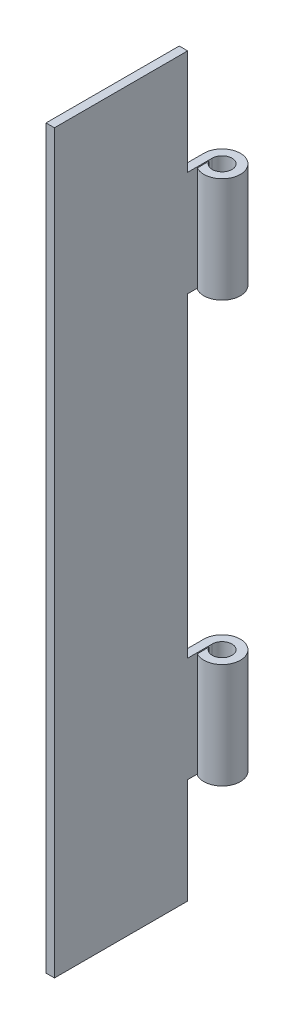
SolidWorks part; units mm, degrees
ref_plane "Front Plane" through (0, 0, 0) normal (0, 0, 1) x (1, 0, 0)
ref_plane "Top Plane" through (0, 0, 0) normal (0, 1, 0) x (1, 0, 0)
ref_plane "Right Plane" through (0, 0, 0) normal (1, 0, 0) x (0, 0, -1)
sketch "Sketch1" plane through (0, 0, 0) normal (1, 0, 0) x (0, 0, -1)
  line L0 (0, 0) -> (0, 88.9) construction
  line L1 (0, 0) -> (19.05, 0) construction
  line L2 (9.144, 12.7) -> (13.1064, 12.7) construction
  line L3 (0, 0) -> (-19.05, 0) construction
  point P3 (11.1252, 12.7)
  point P5 (11.1252, 76.2)
  point P6 (0, 12.7)
  point P9 (-101.6, 88.9)
  point P10 (11.1252, 12.7)
  point P11 (-25.4, 88.9)
  point P12 (-177.8, 88.9)
  point P13 (-11.1252, 76.2)
  point P14 (-11.1252, 12.7)
  dimension "Knuckle Length" = 12.7
  dimension "Length Corner" = 12.7
  dimension "Height Corner" = 7.9248
  dimension "Overall Width" = 38.1
  dimension "Leaf Height" = 88.9
  dimension "MTG Dia" = 3.9624
  dimension "Num Holes" = 101.6
  dimension "Spring Knuckles" = 25.4
  dimension "Num Knuckles" = 177.8
  dimension "D2" = 7.9248
  dimension "Length Corner 2" = 12.7
  dimension "D4" = 12.7
sketch "Sketch2" plane through (0, 0, 0) normal (0, 1, 0) x (1, 0, 0)
  line L0 (1.016, 0) -> (3.3973, 0) construction
  line L1 (0, 19.05) -> (1.016, 19.05) construction
  line L2 (-0.889, 16.1766) -> (0, 16.1766) construction
  line L3 (2.2066, 1.1906) -> (2.2066, 2.2066) construction
  line L5 (2.2066, 2.2066) -> (2.2066, 16.1766) construction
  circle A0 centre (2.2066, 0) radius 1.1906 construction
  point P9 (2.2066, 1.3176)
  point P10 (1.143, 16.1766)
  dimension "Leaf Thickness" = 1.016
  dimension "Pin Dia" = 2.3813
  dimension "Wire Dia" = 0.889
  dimension "Spring Leg Length" = 13.97
  dimension "Bend Clearence" = 0.127
  dimension "D1" = 0.889
  dimension "Open Close Offset" = 2.032
sketch "Sketch3" plane through (0, 0, 0) normal (0, 1, 0) x (1, 0, 0)
  line L0 (1.016, 19.05) -> (0, 19.05)
  line L1 (0, 19.05) -> (0, 0)
  line L2 (0, 0) -> (0, 19.05) construction
  line L3 (1.016, 19.05) -> (1.016, 0)
  line L4 (1.143, 1.9334) -> (1.143, 0.5351)
  arc A0 (0, 0) -> (1.143, 1.9334) centre (2.2066, 0) ccw
  arc A1 (1.016, 0) -> (1.143, 0.5351) centre (2.2066, 0) ccw
extrude "Boss-Extrude1" [suppressed] add sketch "Sketch3" along normal up to vertex
sketch "Sketch4" plane through (0, 0, 0) normal (0, 1, 0) x (1, 0, 0)
  line L0 (0, 0) -> (0, -19.05)
  line L1 (0, -19.05) -> (1.016, -19.05)
  line L2 (1.016, -19.05) -> (1.016, 0)
  line L3 (1.143, -0.5351) -> (1.143, -1.9334)
  line L4 (1.016, 0) -> (3.3973, 0) construction
  line L5 (0, 0) -> (0, 19.05) construction
  arc A0 (1.143, -1.9334) -> (0, 0) centre (2.2066, 0) ccw
  arc A1 (1.143, -0.5351) -> (1.016, 0) centre (2.2066, 0) ccw
extrude "Boss-Extrude2" add sketch "Sketch4" along normal up to vertex (88.9 mm away) separate body up to point (0, 88.9, 0)
sketch "Sketch7" plane through (0, 0, 0) normal (1, 0, 0) x (0, 0, -1)
  line L0 (-2.9686, 76.2) -> (2.9686, 76.2)
  line L1 (-2.9686, 25.4) -> (2.9686, 25.4)
  line L2 (-2.9686, 25.4) -> (-2.9686, 12.7)
  line L3 (-2.9686, 12.7) -> (2.9686, 12.7)
  line L4 (2.9686, 25.4) -> (2.9686, 12.7)
  line L5 (-2.9686, 50.8) -> (2.9686, 50.8)
  line L6 (-2.9686, 50.8) -> (-2.9686, 38.1)
  line L7 (2.9686, 50.8) -> (2.9686, 38.1)
  line L8 (-2.9686, 38.1) -> (2.9686, 38.1)
  line L9 (-2.9686, 25.4) -> (-2.9686, 50.8) construction
  line L10 (-2.9686, 76.2) -> (-2.9686, 63.5)
  line L11 (2.9686, 76.2) -> (2.9686, 63.5)
  line L12 (-2.9686, 63.5) -> (2.9686, 63.5)
  line L13 (-2.9686, 101.6) -> (2.9686, 101.6)
  line L14 (-2.9686, 101.6) -> (-2.9686, 88.9)
  line L15 (2.9686, 101.6) -> (2.9686, 88.9)
  line L16 (-2.9686, 88.9) -> (2.9686, 88.9)
  point P5 (0, 12.7)
  dimension "D2" = 5.9372
  dimension "D3" = 4
extrude "Cut-Extrude2" [suppressed] cut sketch "Sketch7" along normal through all
sketch "Sketch8" plane through (0, 0, 0) normal (1, 0, 0) x (0, 0, -1)
  line L0 (-2.9686, 12.7) -> (2.9686, 12.7) construction
  line L1 (-2.9686, 12.7) -> (2.9686, 12.7)
  line L2 (-2.9686, 12.7) -> (-2.9686, 0)
  line L3 (-2.9686, 0) -> (2.9686, 0)
  line L4 (2.9686, 12.7) -> (2.9686, 0)
  line L5 (-2.9686, 25.4) -> (-2.9686, 12.7) construction
  line L6 (-2.9686, 38.1) -> (2.9686, 38.1)
  line L7 (-2.9686, 38.1) -> (-2.9686, 25.4)
  line L8 (-2.9686, 25.4) -> (2.9686, 25.4)
  line L9 (2.9686, 38.1) -> (2.9686, 25.4)
  line L10 (-2.9686, 12.7) -> (-2.9686, 38.1) construction
  line L11 (-2.9686, 63.5) -> (2.9686, 63.5)
  line L12 (-2.9686, 63.5) -> (-2.9686, 50.8)
  line L13 (-2.9686, 50.8) -> (2.9686, 50.8)
  line L14 (2.9686, 63.5) -> (2.9686, 50.8)
  line L15 (-2.9686, 88.9) -> (2.9686, 88.9)
  line L16 (-2.9686, 88.9) -> (-2.9686, 76.2)
  line L17 (-2.9686, 76.2) -> (2.9686, 76.2)
  line L18 (2.9686, 88.9) -> (2.9686, 76.2)
extrude "Cut-Extrude3" cut sketch "Sketch8" along normal through all
sketch "Sketch10" plane through (0, 0, 0) normal (1, 0, 0) x (0, 0, -1)
  line L1 (2.9686, 50.8) -> (-2.9686, 50.8)
  line L2 (2.9686, 50.8) -> (2.9686, 38.1)
  line L3 (2.9686, 38.1) -> (-2.9686, 38.1)
  line L4 (-2.9686, 50.8) -> (-2.9686, 38.1)
  line L5 (-2.9686, 12.7) -> (2.9686, 12.7) construction
  line L7 (0, 0) -> (0, 88.9) construction
  point P4 (0, 38.1)
  dimension "D2" = 38.1
extrude "Cut-Extrude4" cut sketch "Sketch10" along normal through all
sketch "Sketch9" plane through (0, 0, 0) normal (0, 1, 0) x (1, 0, 0)
  line L0 (1.016, 0) -> (3.3973, 0) construction
  circle A0 centre (2.2066, 0) radius 1.1906
extrude "Boss-Extrude3" [suppressed] add sketch "Sketch9" along normal up to vertex separate body
ref_plane "Plane1" through (0, 38.5445, 0) normal (0, 1, 0) x (1, 0, 0)
sketch "Sketch11" plane through (0, 38.5445, 0) normal (0, 1, 0) x (1, 0, 0)
  circle A0 centre (2.2066, 0) radius 2.2066
curve "Helix/Spiral1" pitch 0.9449 height 11.811 turns 12.5
ref_plane "Plane2" through (0, 50.3555, 0) normal (0, 1, 0) x (1, 0, 0)
sketch "Sketch12" plane through (0, 38.5445, 0) normal (0, 1, 0) x (1, 0, 0)
  line L0 (0, 16.1766) -> (0, 3.3099)
  line L1 (2.2066, 2.2066) -> (1.1033, 2.2066)
  line L2 (-0.889, 16.1766) -> (0, 16.1766) construction
  line L3 (1.1033, 3.3099) -> (1.1033, 2.2066) construction
  arc A0 (1.1033, 2.2066) -> (0, 3.3099) centre (1.1033, 3.3099) cw
sketch "Sketch13" plane through (0, 50.3555, 0) normal (0, 1, 0) x (1, 0, 0)
  line L0 (0, -3.3099) -> (0, -16.1766)
  line L1 (0, 16.1766) -> (0, 3.3099) construction
  line L2 (1.1033, -2.2066) -> (2.2066, -2.2066)
  line L3 (2.2066, 2.2066) -> (1.1033, 2.2066) construction
  arc A0 (0, -3.3099) -> (1.1033, -2.2066) centre (1.1033, -3.3099) cw
  circle A2 centre (2.2066, 0) radius 2.2066 construction
curve "CompCurve1"
ref_plane "Plane3" through (0, 0, -16.1766) normal (0, 0, 1) x (1, 0, 0)
sketch "Sketch14" plane through (0, 0, -16.1766) normal (0, 0, 1) x (1, 0, 0)
  line L0 (-0.4445, 0) -> (-0.4445, 38.5445) construction
  line L1 (-0.889, 0) -> (0, 0) construction
  line L3 (4.4132, 38.5445) -> (0, 38.5445) construction
  circle A0 centre (-0.4445, 38.5445) radius 0.4445
  dimension "D1" = 0.889
sweep "Sweep1" [suppressed] add profiles "Sketch14" path "CompCurve1"
sketch "Sketch15" plane through (0, 0, 0) normal (1, 0, 0) x (0, 0, -1)
  line L0 (9.144, 12.7) -> (13.1064, 12.7) construction
  circle A0 centre (11.1252, 12.7) radius 1.9812
  circle A1 centre (-11.1252, 12.7) radius 1.9812
  dimension "D1" = 22.2504
extrude "Cut-Extrude5" [suppressed] cut sketch "Sketch15" along normal through all
ref_plane "Mid Plane" [suppressed] through (0, 44.45, 0) normal (0, -1, 0) x (-1, 0, 0)
mirror "Mirror1" [suppressed] about plane through (0, 44.45, 0) normal (0, -1, 0)
equation "\"Num Knuckles\"=5"
equation "\"D1@Sketch7\"=\"Knuckle Length@Sketch1\""
equation "\"D2@Sketch7\" = ( 2 * \"Leaf Thickness@Sketch2\" ) + \"Pin Dia@Sketch2\" + ( .04 * \"Overall Width@Sketch1\" )"
equation "\"D4@Sketch7\"=\"Knuckle Length@Sketch1\"*2"
equation "\"D3@Sketch7\" = int ( \"Num Knuckles@Sketch1\" / 2 )  + 1"
equation "\"D2@Sketch8\"=\"D4@Sketch7\""
equation "\"D1@Sketch8\"=\"D3@Sketch7\""
equation "\"Spring Knuckles\"= 1"
equation "\"D1@Sketch10\"= \"Knuckle Length@Sketch1\" * \"Spring Knuckles@Sketch1\""
equation "\"D2@Sketch10\"=\"Knuckle Length@Sketch1\"*(\"Num Knuckles@Sketch1\"-\"Spring Knuckles@Sketch1\")/2"
equation "\"D1@Plane1\"=\"D2@Sketch10\"+(\"Wire Dia@Sketch2\"/2)"
equation "\"D3@Helix/Spiral1\"=(\"Spring Knuckles@Sketch1\"*\"Knuckle Length@Sketch1\")-\"Wire Dia@Sketch2\""
equation "\"D1@Plane2\"=\"D3@Helix/Spiral1\""
equation "\"D1@Sketch14\"=\"Wire Dia@Sketch2\""
equation "\"Num Holes\"=4"
equation "\"D1@Sketch1\"=\"Length Corner@Sketch1\""
equation "\"D1@Sketch2\"= \"Wire Dia@Sketch2\""
equation "\"Knuckle Length@Sketch1\"=\"Leaf Height@Sketch1\"/\"Num Knuckles@Sketch1\""
equation "\"D2@Sketch1\"=\"Height Corner@Sketch1\""
equation "\"D4@Sketch1\" = \"Length Corner 2@Sketch1\""
